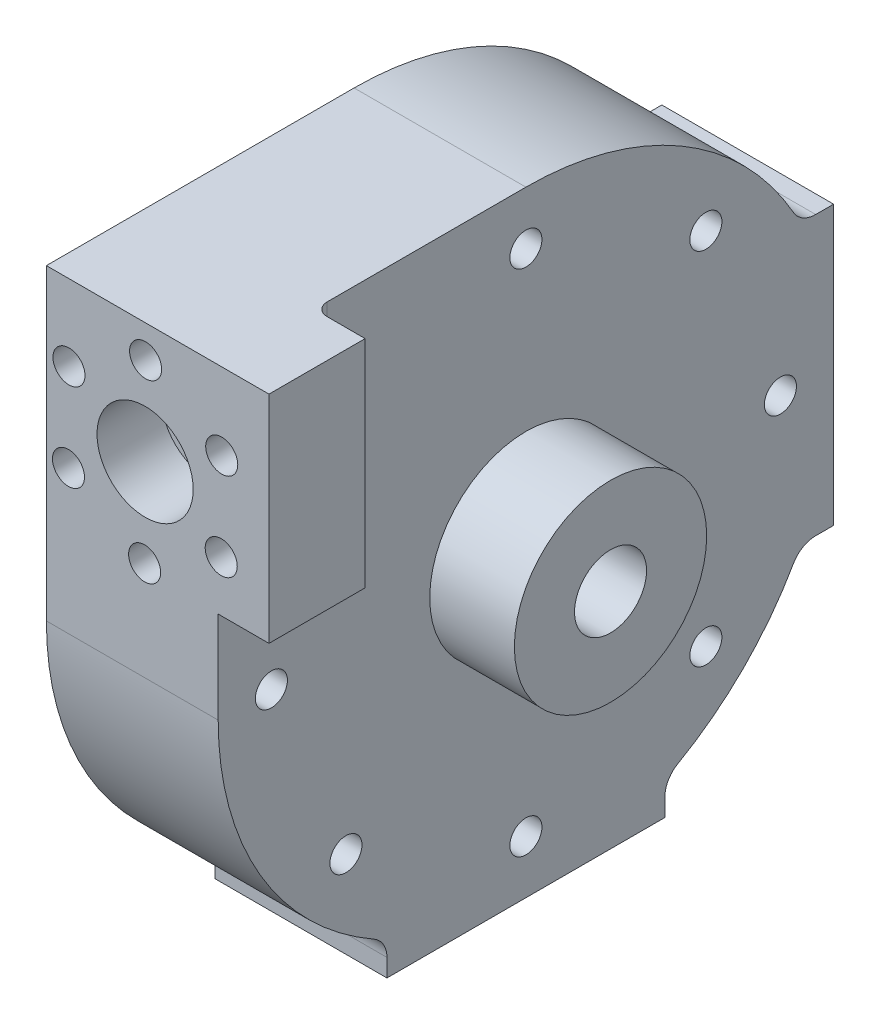
SolidWorks part; units mm, degrees
ref_plane "Front Plane" through (0, 0, 0) normal (0, 0, 1) x (1, 0, 0)
ref_plane "Top Plane" through (0, 0, 0) normal (0, 1, 0) x (1, 0, 0)
ref_plane "Right Plane" through (0, 0, 0) normal (1, 0, 0) x (0, 0, -1)
sketch "Sketch1" plane through (0, 0, 0) normal (1, 0, 0) x (0, 0, -1)
  line L0 (-60.96, 0) -> (-60.96, 60.96)
  line L1 (-60.96, 60.96) -> (0, 60.96)
  line L2 (-27.53, -60.96) -> (27.53, -60.96)
  line L3 (27.53, -60.96) -> (27.53, -54.3895)
  line L4 (0, 55) -> (0, -55) construction
  line L5 (-27.53, -60.96) -> (-27.53, -54.3895)
  line L6 (60.96, 27.559) -> (60.96, -27.559)
  line L7 (60.96, -27.559) -> (54.3748, -27.559)
  line L8 (55, 0) -> (-55, 0) construction
  line L9 (60.96, 27.559) -> (54.3748, 27.559)
  arc A1 (-60.96, 0) -> (-27.53, -54.3895) centre (0, 0) ccw
  arc A2 (27.53, -54.3895) -> (54.3748, -27.559) centre (0, 0) ccw
  arc A3 (54.3748, 27.559) -> (0, 60.96) centre (0, 0) ccw
  point P17 (60.96, 0)
extrude "Housing 2" add sketch "Sketch1" along normal blind 44.45 contours L0 L1 A3 L9 L6 L7 A2 L3 L2 L5 A1
sketch "Sketch2" plane through (0, 0, 0) normal (-1, 0, 0) x (0, 0, 1)
  circle A0 centre (0, 0) radius 43.815
extrude "Impeller Cut" cut sketch "Sketch2" against normal blind 22.4028
sketch "Sketch3" plane through (0, 0, 0) normal (0, 0, 1) x (1, 0, 0)
  line L2 (29.6028, 9.6415) -> (22.4028, 43.815)
  line L3 (29.6028, 9.6415) -> (29.6028, 0)
  line L4 (44.45, 0) -> (0, 0) construction
  line L7 (22.4028, 43.815) -> (22.225, 0)
  line L8 (22.225, 0) -> (29.6028, 0)
revolve "Impeller Angle Cut" cut sketch "Sketch3" angle 360 about L8
sketch "Sketch4" plane through (29.6028, 0, 0) normal (-1, 0, 0) x (0, 0, 1)
  circle A0 centre (0, 0) radius 4.826
extrude "Inlet Cut" cut sketch "Sketch4" against normal blind 19.8628
sketch "Sketch5" plane through (44.45, 0, 0) normal (1, 0, 0) x (0, 0, -1)
  circle A1 centre (0, 19.05) radius 1.5875
extrude "Inlet Fastener Bore" [suppressed] cut sketch "Sketch5" against normal blind 6.35
pattern_circular "Inlet Fastener Pattern" [suppressed] count 6 over 360 of bodies 107
sketch "Sketch6" plane through (44.45, 0, 0) normal (1, 0, 0) x (0, 0, -1)
  circle A2 centre (50.419, 0) radius 3.175
extrude "Fastener Bore" cut sketch "Sketch6" against normal blind 116.84
pattern_circular "Fastener Pattern" count 8 over 360 about axis through (22.4028, 0, 0) along (-1, 0, 0) skipping 5 of "Fastener Bore"
sketch "Sketch7" plane through (44.45, 0, 0) normal (1, 0, 0) x (0, 0, -1)
  circle A0 centre (0, 0) radius 19.05
  circle A1 centre (0, 0) radius 100.1143
extrude "Mass Reduction Cut" cut sketch "Sketch7" against normal blind 10.414
fillet "Fillet3" [suppressed] radius 5.08
sketch "Sketch8" plane through (0, 0, 60.96) normal (0, 0, 1) x (1, 0, 0)
  line L0 (34.036, 0) -> (34.036, 60.96) construction
  line L1 (0, 60.96) -> (34.036, 60.96)
  line L2 (0, 60.96) -> (0, 10.1635)
  line L3 (0, 10.1635) -> (34.036, 10.1635)
  line L4 (34.036, 60.96) -> (34.036, 10.1635)
extrude "Discharge Cut" [suppressed] cut sketch "Sketch8" against normal blind 2.54
fillet "Fillet4" [suppressed] radius 5.08
sketch "Sketch9" [suppressed] plane through (0, 0, 58.42) normal (0, 0, 1) x (1, 0, 0)
  circle A0 centre (19.6343, 36.5011) radius 2.54
extrude "Discharge Bore" [suppressed] cut sketch "Sketch9" against normal blind 50.038
sketch "Sketch11" plane through (44.45, 0, 0) normal (1, 0, 0) x (0, 0, -1)
  circle A0 centre (0, 0) radius 19.05
  circle A1 centre (0, 0) radius 4.826
extrude "Boss-Extrude1" add sketch "Sketch11" along normal blind 6.35
sketch "Sketch12" [suppressed] plane through (56.896, 0, 0) normal (1, 0, 0) x (0, 0, -1)
  circle A0 centre (19.976, 0) radius 3.175
extrude "Cut-Extrude1" [suppressed] cut sketch "Sketch12" against normal blind 19.05
pattern_circular "CirPattern1" [suppressed] count 6 over 360 of bodies 116
fillet "Fillet6" [suppressed] radius 2.54
sketch "Sketch13" [suppressed] plane through (0, 0, 58.42) normal (0, 0, 1) x (1, 0, 0)
  circle A0 centre (19.6343, 36.5011) radius 9.525
extrude "Cut-Extrude2" [suppressed] cut sketch "Sketch13" against normal blind 25.4
sketch "Sketch14" plane through (0, 0, 0) normal (0, 0, 1) x (1, 0, 0)
  circle A0 centre (19.558, 37.084) radius 2.3813
extrude "Cut-Extrude3" cut sketch "Sketch14" along normal blind 99.06
sketch "Sketch15" plane through (0, 0, 60.96) normal (0, 0, 1) x (1, 0, 0)
  circle A0 centre (19.558, 37.084) radius 9.525
extrude "Cut-Extrude4" cut sketch "Sketch15" against normal blind 25.4
sketch "Sketch16" plane through (0, 0, 35.56) normal (0, 0, 1) x (1, 0, 0)
  circle A0 centre (19.558, 37.084) radius 9.525
  circle A1 centre (19.558, 37.084) radius 6.35
extrude "Boss-Extrude2" add sketch "Sketch16" along normal blind 12.7
sketch "Sketch18" plane through (0, 0, 60.96) normal (0, 0, 1) x (1, 0, 0)
  line L1 (34.036, 60.96) -> (44.0965, 60.96)
  line L2 (34.036, 60.96) -> (34.036, 18.1962)
  line L3 (34.036, 18.1962) -> (44.0965, 18.1962)
  line L4 (44.0965, 60.96) -> (44.0965, 18.1962)
extrude "Boss-Extrude3" add sketch "Sketch18" against normal blind 19.05
fillet "Fillet7" radius 2.54 1 edges at (34.036, 39.5781, 41.91)
sketch "Sketch19" plane through (0, 0, 60.96) normal (0, 0, 1) x (1, 0, 0)
  circle A0 centre (19.4606, 19.6119) radius 3.175
  circle A1 centre (34.6406, 28.2636) radius 3.175
  circle A2 centre (34.738, 45.7357) radius 3.175
  circle A3 centre (19.6554, 54.5561) radius 3.175
  circle A4 centre (4.4754, 45.9044) radius 3.175
  circle A5 centre (4.378, 28.4323) radius 3.175
extrude "Cut-Extrude5" cut sketch "Sketch19" against normal blind 15.24
fillet "Fillet8" [suppressed] radius 2.54
ref_plane "Plane1" [suppressed] through (34.036, -60.96, 27.53) normal (0, 0, -1) x (-1, 0, 0)
ref_plane "Plane2" [suppressed] through (34.036, -60.96, -27.53) normal (0, 0, -1) x (-1, 0, 0)
fillet "Fillet9" radius 5.08 4 edges at (17.018, -27.559, -54.3748) (17.018, 27.559, -54.3748) (17.018, -54.3895, -27.53) (17.018, -54.3895, 27.53)
sketch "Sketch20" plane through (0, 60.96, 0) normal (0, 1, 0) x (1, 0, 0)
  circle A0 centre (19.8775, -40.3269) radius 0.6493
extrude "Cut-Extrude6" [suppressed] cut sketch "Sketch20" against normal blind 51.562
sketch "Sketch21" [suppressed] plane through (0, 60.96, 0) normal (0, 1, 0) x (1, 0, 0)
  circle A0 centre (19.8775, -40.3269) radius 4.7625
extrude "Cut-Extrude7" [suppressed] cut sketch "Sketch21" against normal blind 6.35
sketch "Sketch22" plane through (50.8, 0, 0) normal (1, 0, 0) x (0, 0, -1)
  circle A0 centre (0, 0) radius 7.1374
extrude "Cut-Extrude8" cut sketch "Sketch22" against normal blind 17.78
